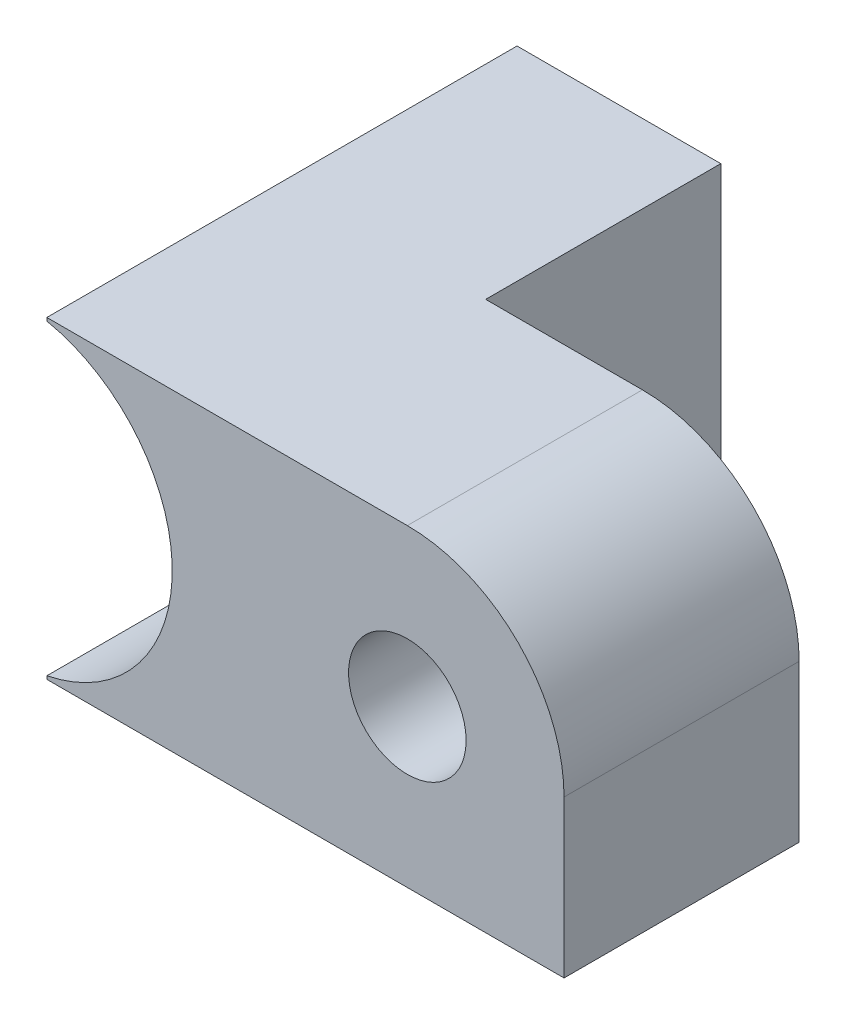
SolidWorks part; units mm, degrees
material "AISI Type A2 Tool Steel Custom"
ref_plane "Front Plane" through (0, 0, 0) normal (0, 0, 1) x (1, 0, 0)
ref_plane "Top Plane" through (0, 0, 0) normal (0, 1, 0) x (1, 0, 0)
ref_plane "Right Plane" through (0, 0, 0) normal (1, 0, 0) x (0, 0, -1)
sketch "Sketch1" plane through (0, 0, 0) normal (0, 0, 1) x (1, 0, 0)
  line L1 (2.54, 0) -> (44.45, 0)
  line L3 (2.54, 25.4) -> (31.75, 25.4)
  line L4 (44.45, 0) -> (44.45, 12.7)
  line L5 (2.54, 25.4) -> (2.54, 25.1434)
  line L8 (2.54, 0.2566) -> (2.54, 0)
  arc A1 (2.54, 0.2566) -> (2.54, 25.1434) centre (0, 12.7) ccw
  arc A2 (44.45, 12.7) -> (31.75, 25.4) centre (31.75, 12.7) ccw
  point P6 (35.6806, 10.2806)
  point P12 (40.1314, 13.0818)
  dimension "D2" = 25.4
  dimension "D1" = 44.45
  dimension "D3" = 12.7
  dimension "D4" = 2.54
  dimension "D7" = 0.2566
extrude "Boss-Extrude1" add sketch "Sketch1" along normal blind 38.1
sketch "Sketch2" plane through (0, 0, 0) normal (0, 0, -1) x (-1, 0, 0)
  line L0 (-19.05, 0) -> (-19.05, 25.4)
  line L3 (-2.54, 0) -> (-44.45, 0) construction
  line L4 (-31.75, 25.4) -> (-2.54, 25.4) construction
  line L8 (-19.05, 0) -> (-44.45, 0)
  line L9 (-31.75, 25.4) -> (-2.54, 25.4) construction
  line L11 (-44.45, 0) -> (-44.45, 12.7) construction
  line L13 (-44.45, 0) -> (-44.45, 12.7)
  line L14 (-31.75, 25.4) -> (-19.05, 25.4)
  arc A0 (-31.75, 25.4) -> (-44.45, 12.7) centre (-31.75, 12.7) ccw construction
  arc A2 (-31.75, 25.4) -> (-44.45, 12.7) centre (-31.75, 12.7) ccw
  dimension "D1" = 19.05
extrude "Cut-Extrude1" cut sketch "Sketch2" against normal blind 19.05
sketch "Sketch3" plane through (0, 0, 38.1) normal (0, 0, 1) x (1, 0, 0)
  arc A0 (44.45, 12.7) -> (31.75, 25.4) centre (31.75, 12.7) ccw construction
  point P0 (31.75, 12.7)
hole_wizard "3/8 (0.375) Diameter Hole1" positions "Sketch3" profile "Sketch4" hole size "3/8" standard "ANSI Inch" end condition through all
sketch "Sketch4" plane through (31.75, 12.7, 38.1) normal (1, 0, 0) x (0, -1, 0)
  line L0 (0, 0) -> (0, 38.1)
  line L1 (0, 38.1) -> (4.7625, 38.1)
  line L2 (4.7625, 38.1) -> (4.7625, 0)
  line L5 (4.7625, 0) -> (0, 0)
  line L11 (0, -6.35) -> (0, 107.95) construction
  dimension "Thru Hole Dia." = 9.525
  dimension "Thru Hole Depth" = 38.1
chamfer "Chamfer1" distance 1.27 angle 45 1 edges at (19.05, 0, 9.525)
